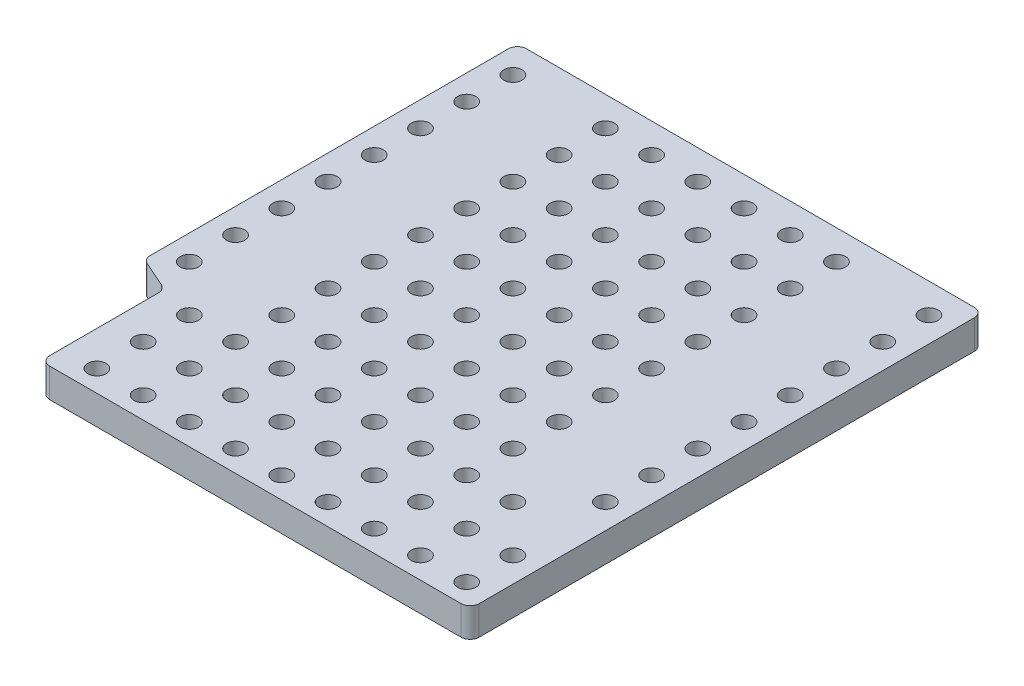
SolidWorks part; units mm, degrees
ref_plane "Front Plane" through (0, 0, 0) normal (0, 0, 1) x (1, 0, 0)
ref_plane "Top Plane" through (0, 0, 0) normal (0, 1, 0) x (1, 0, 0)
ref_plane "Right Plane" through (0, 0, 0) normal (1, 0, 0) x (0, 0, -1)
sketch "Sketch2" plane through (0, 0, 0) normal (0, 1, 0) x (1, 0, 0)
  line L0 (-11.43, 26.58) -> (11.43, 26.58) construction
  line L2 (-12.8, 7.6905) -> (-12.8, 28.2)
  line L3 (-12.8, 28.2) -> (12.8, 28.2)
  line L4 (12.8, 0) -> (12.8, 28.2)
  line L5 (0, 0) -> (0, 28.2) construction
  line L6 (-11.43, 26.58) -> (-11.43, 24.04) construction
  line L7 (-130.1532, 224.7802) -> (936.5135, 224.7802) construction
  line L10 (-12.8, 0) -> (-12.8, 7.6905) construction
  line L11 (-12.8, 0) -> (-10.8, 0) construction
  line L12 (-10.8, 0) -> (12.8, 0)
  line L14 (-10.8, 0) -> (-10.8, 6.8)
  line L15 (-10.8, 6.8) -> (-12.8, 7.6905)
  line L16 (223.547, 458.7027) -> (1290.2137, 458.7027) construction
  circle A0 centre (-11.43, 26.58) radius 0.5
  circle A1 centre (11.43, 26.58) radius 0.5
  circle A2 centre (-11.43, 24.04) radius 0.5
  circle A3 centre (11.43, 24.04) radius 0.5
  circle A4 centre (-11.43, 21.5) radius 0.5
  circle A5 centre (11.43, 21.5) radius 0.5
  circle A6 centre (-11.43, 18.96) radius 0.5
  circle A7 centre (11.43, 18.96) radius 0.5
  circle A8 centre (-11.43, 16.42) radius 0.5
  circle A9 centre (11.43, 16.42) radius 0.5
  circle A10 centre (-11.43, 13.88) radius 0.5
  circle A11 centre (11.43, 13.88) radius 0.5
  circle A12 centre (-11.43, 11.34) radius 0.5
  circle A13 centre (11.43, 11.34) radius 0.5
  circle A14 centre (-11.43, 8.8) radius 0.5
  circle A15 centre (11.43, 8.8) radius 0.5
  point P12 (0, 26.58)
  dimension "D3" = 1
  dimension "D1" = 6.8
  dimension "D2" = 28.2
  dimension "D4" = 22.86
  dimension "D5" = 1.62
  dimension "D7" = 2.54
  dimension "D8" = 25.6
  dimension "D9" = 114
  dimension "D10" = 2
  dimension "D6" = 8
extrude "Boss-Extrude1" add sketch "Sketch2" along normal blind 1.6
sketch "Sketch3" plane through (0, 0, 0) normal (0, -1, 0) x (1, 0, 0)
  line L0 (-11.43, -26.58) -> (-6.35, -26.58) construction
  line L1 (-6.35, -26.58) -> (-3.81, -26.58) construction
  line L2 (-6.35, -26.58) -> (-6.35, -24.04) construction
  line L3 (-8.89, -26.58) -> (-8.89, -6.26) construction
  line L4 (-8.89, -6.26) -> (-6.35, -6.26) construction
  line L5 (-8.89, -6.26) -> (-8.89, -3.72) construction
  circle A0 centre (-6.35, -26.58) radius 0.5
  circle A1 centre (-3.81, -26.58) radius 0.5
  circle A2 centre (-1.27, -26.58) radius 0.5
  circle A3 centre (1.27, -26.58) radius 0.5
  circle A4 centre (3.81, -26.58) radius 0.5
  circle A5 centre (6.35, -26.58) radius 0.5
  circle A6 centre (-3.81, -24.04) radius 0.5
  circle A7 centre (-1.27, -24.04) radius 0.5
  circle A8 centre (1.27, -24.04) radius 0.5
  circle A9 centre (3.81, -24.04) radius 0.5
  circle A10 centre (6.35, -24.04) radius 0.5
  circle A11 centre (-3.81, -21.5) radius 0.5
  circle A12 centre (-1.27, -21.5) radius 0.5
  circle A13 centre (1.27, -21.5) radius 0.5
  circle A14 centre (3.81, -21.5) radius 0.5
  circle A15 centre (6.35, -21.5) radius 0.5
  circle A16 centre (-3.81, -18.96) radius 0.5
  circle A17 centre (-1.27, -18.96) radius 0.5
  circle A18 centre (1.27, -18.96) radius 0.5
  circle A19 centre (3.81, -18.96) radius 0.5
  circle A20 centre (6.35, -18.96) radius 0.5
  circle A21 centre (-3.81, -16.42) radius 0.5
  circle A22 centre (-1.27, -16.42) radius 0.5
  circle A23 centre (1.27, -16.42) radius 0.5
  circle A24 centre (3.81, -16.42) radius 0.5
  circle A25 centre (6.35, -16.42) radius 0.5
  circle A26 centre (-3.81, -13.88) radius 0.5
  circle A27 centre (-1.27, -13.88) radius 0.5
  circle A28 centre (1.27, -13.88) radius 0.5
  circle A29 centre (3.81, -13.88) radius 0.5
  circle A30 centre (6.35, -13.88) radius 0.5
  circle A31 centre (-3.81, -11.34) radius 0.5
  circle A32 centre (-1.27, -11.34) radius 0.5
  circle A33 centre (1.27, -11.34) radius 0.5
  circle A34 centre (3.81, -11.34) radius 0.5
  circle A35 centre (6.35, -11.34) radius 0.5
  circle A36 centre (-3.81, -8.8) radius 0.5
  circle A37 centre (-1.27, -8.8) radius 0.5
  circle A38 centre (1.27, -8.8) radius 0.5
  circle A39 centre (3.81, -8.8) radius 0.5
  circle A40 centre (6.35, -8.8) radius 0.5
  circle A56 centre (-6.35, -24.04) radius 0.5
  circle A57 centre (-6.35, -21.5) radius 0.5
  circle A58 centre (-6.35, -18.96) radius 0.5
  circle A59 centre (-6.35, -16.42) radius 0.5
  circle A60 centre (-6.35, -13.88) radius 0.5
  circle A61 centre (-6.35, -11.34) radius 0.5
  circle A62 centre (-6.35, -8.8) radius 0.5
  circle A66 centre (-8.89, -6.26) radius 0.5
  circle A67 centre (-6.35, -6.26) radius 0.5
  circle A68 centre (-3.81, -6.26) radius 0.5
  circle A69 centre (-1.27, -6.26) radius 0.5
  circle A70 centre (1.27, -6.26) radius 0.5
  circle A71 centre (3.81, -6.26) radius 0.5
  circle A72 centre (6.35, -6.26) radius 0.5
  circle A73 centre (8.89, -6.26) radius 0.5
  circle A74 centre (-6.35, -3.72) radius 0.5
  circle A75 centre (-3.81, -3.72) radius 0.5
  circle A76 centre (-1.27, -3.72) radius 0.5
  circle A77 centre (1.27, -3.72) radius 0.5
  circle A78 centre (3.81, -3.72) radius 0.5
  circle A79 centre (6.35, -3.72) radius 0.5
  circle A80 centre (8.89, -3.72) radius 0.5
  circle A81 centre (-6.35, -1.18) radius 0.5
  circle A82 centre (-3.81, -1.18) radius 0.5
  circle A83 centre (-1.27, -1.18) radius 0.5
  circle A84 centre (1.27, -1.18) radius 0.5
  circle A85 centre (3.81, -1.18) radius 0.5
  circle A86 centre (6.35, -1.18) radius 0.5
  circle A87 centre (8.89, -1.18) radius 0.5
  circle A88 centre (-8.89, -3.72) radius 0.5
  circle A89 centre (-8.89, -1.18) radius 0.5
  circle A91 centre (11.43, -3.72) radius 0.5
  circle A92 centre (11.43, -1.18) radius 0.5
  circle A93 centre (11.43, -6.26) radius 0.5 [skipped]
  dimension "D2" = 1
  dimension "D1" = 5.08
  dimension "D5" = 2.54
  dimension "D6" = 2.54
  dimension "D7" = 20.32
  dimension "D10" = 2.54
  dimension "D11" = 2.54
  dimension "D3" = 6
  dimension "D4" = 8
  dimension "D8" = 9
  dimension "D9" = 3
fillet "Fillet1" radius 0.5 6 edges at (-10.8, 0.8, 0) (-10.8, 0.8, -6.8) (-12.8, 0.8, -7.6905) (-12.8, 0.8, -28.2) (12.8, 0.8, -28.2) (12.8, 0.8, 0)
ref_axis "Axis1" through (-11.43, 1.6, -26.58) along (0, -1, 0)
ref_axis "Axis2" through (11.43, 1.6, -26.58) along (0, -1, 0)
ref_axis "Axis3" through (-11.43, 1.6, -8.8) along (0, -1, 0)
ref_axis "Axis4" through (11.43, 1.6, -8.8) along (0, -1, 0)
extrude "Cut-Extrude1" cut sketch "Sketch3" against normal through all
